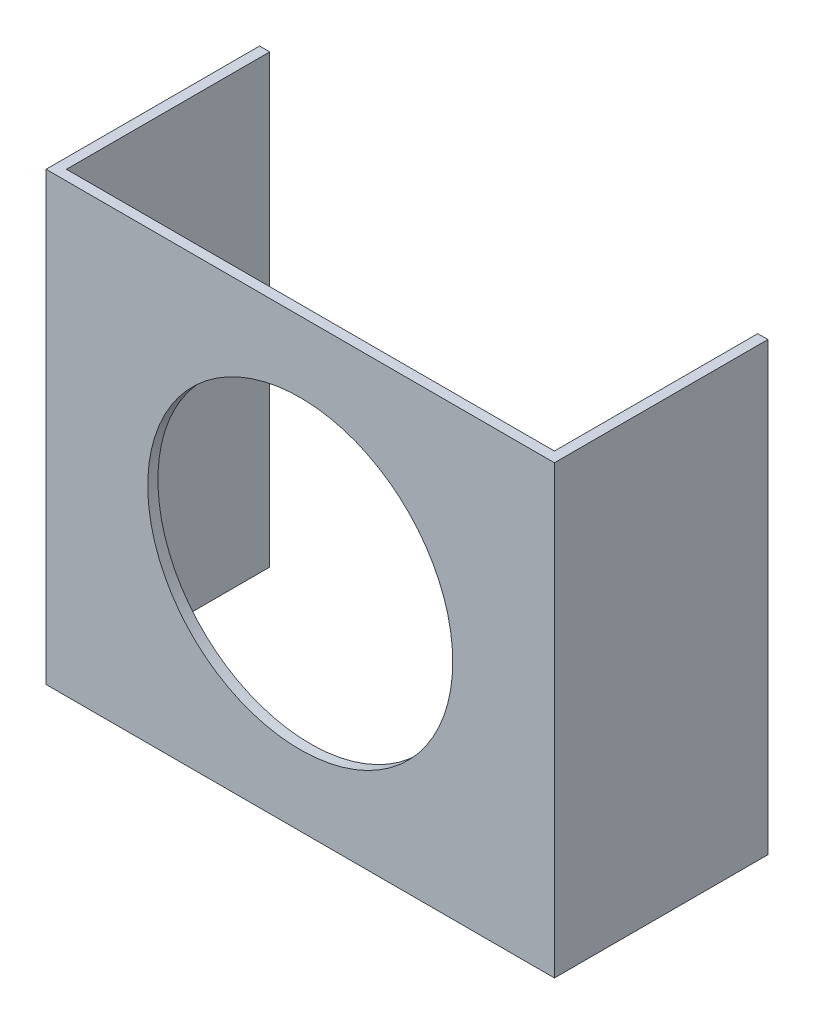
SolidWorks part; units mm, degrees
ref_plane "Front Plane" through (0, 0, 0) normal (0, 0, 1) x (1, 0, 0)
ref_plane "Top Plane" through (0, 0, 0) normal (0, 1, 0) x (1, 0, 0)
ref_plane "Right Plane" through (0, 0, 0) normal (1, 0, 0) x (0, 0, -1)
sketch "Sketch1" plane through (0, 0, 0) normal (0, 0, 1) x (1, 0, 0)
  line L0 (20, -16) -> (20, 16) construction
  line L1 (-25, 21.9442) -> (25, 21.9442)
  line L2 (-25, 21.9442) -> (-25, -21.9442)
  line L3 (-25, -21.9442) -> (25, -21.9442)
  line L4 (25, 21.9442) -> (25, -21.9442)
  line L5 (-25, 21.9442) -> (25, -21.9442) construction
  line L6 (-25, -21.9442) -> (25, 21.9442) construction
  point P0 (0, 0)
  dimension "D1" = 5
extrude "Boss-Extrude1" add sketch "Sketch1" along normal blind 1
sketch "Sketch2" plane through (0, 0, 0) normal (0, 0, -1) x (-1, 0, 0)
  line L0 (-25, 21.9442) -> (-25, -21.9442)
  line L2 (25, -21.9442) -> (-25, -21.9442) construction
  line L3 (-24, -21.9442) -> (-24, 21.9442)
  line L4 (-25, 21.9442) -> (25, 21.9442) construction
  line L7 (25, 21.9442) -> (25, -21.9442) construction
  line L8 (25, 21.0013) -> (25, 21.9442)
  line L9 (24, -21.9442) -> (25, -21.9442)
  line L10 (24, 21.9442) -> (24, -21.9442)
  line L11 (24, 21.9442) -> (25, 21.9442)
  line L12 (25, -21.9442) -> (25, 21.9442)
  line L13 (-25, 21.9442) -> (-24, 21.9442)
  line L15 (-25, -21.9442) -> (-24, -21.9442)
  line M12 (-25, -21.9442) -> (25, -21.9442)
  line M13 (25, -21.9442) -> (25, 21.9442)
  line M14 (25, 21.9442) -> (-25, 21.9442)
  dimension "D1" = 1
  dimension "D3" = 1
extrude "Boss-Extrude3" add sketch "Sketch2" along normal blind 20 contours L10 M14 M12 M13 | L0 L15 L3 L13 region at (-24.5, 0, 0)
sketch "Sketch3" plane through (0, 0, 1) normal (0, 0, 1) x (1, 0, 0)
  circle A0 centre (0, 0) radius 15
  dimension "D1" = 30
extrude "Cut-Extrude1" cut sketch "Sketch3" against normal through all
